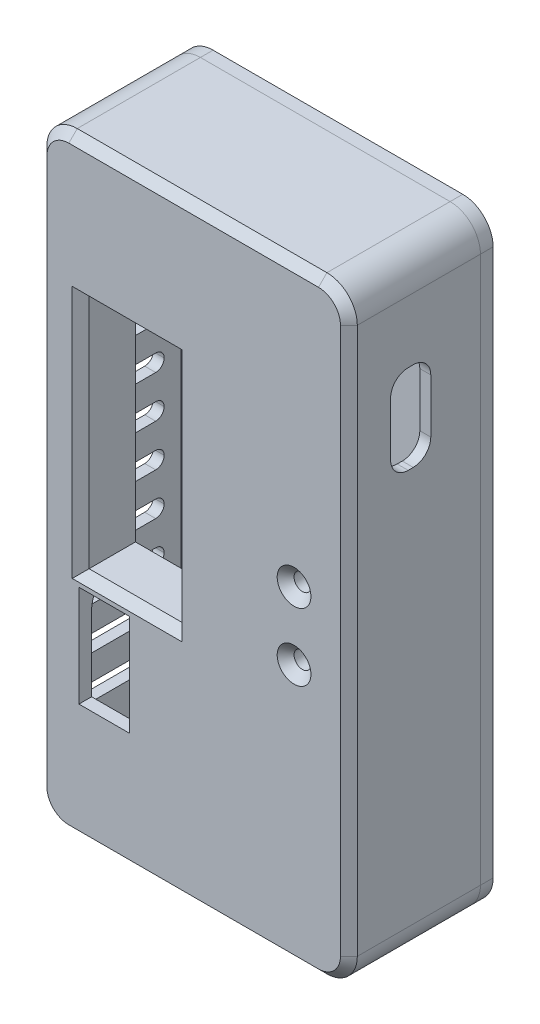
SolidWorks part; units mm, degrees
ref_plane "Front Plane" through (0, 0, 0) normal (0, 0, 1) x (1, 0, 0)
ref_plane "Top Plane" through (0, 0, 0) normal (0, 1, 0) x (1, 0, 0)
ref_plane "Right Plane" through (0, 0, 0) normal (1, 0, 0) x (0, 0, -1)
sketch "Sketch1" plane through (0, 0, 0) normal (0, 0, 1) x (1, 0, 0)
  line L0 (1226.9658, 17.5347) -> (1226.9658, 3.5347) construction
  line L1 (1226.9658, -40.4653) -> (1226.9658, -54.4653) construction
  line L2 (1260.1694, 17.5347) -> (1226.9658, 17.5347) construction
  line L3 (1263.7694, -50.8653) -> (1263.7694, 13.9347) construction
  line L4 (1226.9658, -54.4653) -> (1260.1694, -54.4653) construction
  line L5 (1226.9658, 17.5347) -> (1226.9658, 3.5347)
  line L6 (1226.9658, 3.5347) -> (1226.9658, -54.4653)
  line L7 (1260.1694, 17.5347) -> (1226.9658, 17.5347)
  line L8 (1263.7694, -50.8653) -> (1263.7694, 13.9347)
  line L9 (1226.9658, -54.4653) -> (1260.1694, -54.4653)
  line L10 (1228.2658, -53.1653) -> (1260.1694, -53.1653)
  line L11 (1262.4694, -50.8653) -> (1262.4694, 13.9347)
  line L12 (1260.1694, 16.2347) -> (1228.2658, 16.2347)
  line L13 (1228.2658, 16.2347) -> (1228.2658, 3.5347)
  line L14 (1228.2658, 3.5347) -> (1228.2658, -53.1653)
  arc A0 (1263.7694, 13.9347) -> (1260.1694, 17.5347) centre (1260.1694, 13.9347) ccw construction
  arc A1 (1260.1694, -54.4653) -> (1263.7694, -50.8653) centre (1260.1694, -50.8653) ccw construction
  arc A2 (1263.7694, 13.9347) -> (1260.1694, 17.5347) centre (1260.1694, 13.9347) ccw
  arc A3 (1260.1694, -54.4653) -> (1263.7694, -50.8653) centre (1260.1694, -50.8653) ccw
  arc A4 (1260.1694, -53.1653) -> (1262.4694, -50.8653) centre (1260.1694, -50.8653) ccw
  arc A5 (1262.4694, 13.9347) -> (1260.1694, 16.2347) centre (1260.1694, 13.9347) ccw
  dimension "D1" = 1.3
extrude "Boss-Extrude1" add sketch "Sketch1" along normal offset from surface (14.1005 mm away) 0.2 offset beyond the face yes
sketch "Sketch2" plane through (0, 0, 14.1005) normal (0, 0, 1) x (1, 0, 0)
  line L5 (1226.9658, 17.5347) -> (1226.9658, -54.4653)
  line L6 (1226.9658, -54.4653) -> (1260.1694, -54.4653)
  line L7 (1263.7694, -50.8653) -> (1263.7694, 13.9347)
  line L8 (1260.1694, 17.5347) -> (1226.9658, 17.5347)
  line L9 (1226.9658, 17.5347) -> (1226.9658, -54.4653)
  line L10 (1226.9658, -54.4653) -> (1260.1694, -54.4653)
  line L11 (1263.7694, -50.8653) -> (1263.7694, 13.9347)
  line L12 (1260.1694, 17.5347) -> (1226.9658, 17.5347)
  arc A2 (1260.1694, -54.4653) -> (1263.7694, -50.8653) centre (1260.1694, -50.8653) ccw
  arc A3 (1263.7694, 13.9347) -> (1260.1694, 17.5347) centre (1260.1694, 13.9347) ccw
  arc A4 (1260.1694, -54.4653) -> (1263.7694, -50.8653) centre (1260.1694, -50.8653) ccw
  arc A5 (1263.7694, 13.9347) -> (1260.1694, 17.5347) centre (1260.1694, 13.9347) ccw
  dimension "D1" = 0
extrude "Boss-Extrude2" add sketch "Sketch2" along normal blind 1.5
sketch "Sketch3" plane through (0, 0, 15.6005) normal (0, 0, 1) x (1, 0, 0)
  line L0 (1226.9658, -40.4653) -> (1226.9658, -54.4653) construction
  line L1 (1231.7658, -28.4653) -> (1237.7658, -28.4653)
  line L2 (1231.7658, -28.4653) -> (1231.7658, -40.4653)
  line L3 (1231.7658, -40.4653) -> (1237.7658, -40.4653)
  line L4 (1237.7658, -28.4653) -> (1237.7658, -40.4653)
  line L5 (1231.9658, -26.9653) -> (1242.9658, -26.9653)
  line L6 (1231.9658, -26.9653) -> (1231.9658, 1.0347)
  line L7 (1231.9658, 1.0347) -> (1242.9658, 1.0347)
  line L8 (1242.9658, -26.9653) -> (1242.9658, 1.0347)
  line L9 (1226.9658, -54.4653) -> (1260.1694, -54.4653) construction
  line L10 (1257.2694, -15.6653) -> (1257.2694, -23.6653) construction
  line L11 (1263.7694, -50.8653) -> (1263.7694, 13.9347) construction
  circle A0 centre (1257.2694, -23.6653) radius 1
  circle A1 centre (1257.2694, -15.6653) radius 1
  point P18 (1237.4658, -26.9653)
  dimension "D1" = 6
  dimension "D5" = 2
  dimension "D2" = 4.8
  dimension "D3" = 12
  dimension "D4" = 14
  dimension "D6" = 6.5
  dimension "D7" = 30.8
  dimension "D8" = 8
  dimension "D9" = 11
  dimension "D10" = 28
  dimension "D11" = 27.5
  dimension "D12" = 5
extrude "Cut-Extrude1" cut sketch "Sketch3" against normal blind 3.5
sketch "Sketch4" plane through (0, -54.4653, 0) normal (0, -1, 0) x (1, 0, 0)
  circle A2 centre (1247.2906, 10.2505) radius 3.8
  circle A3 centre (1247.2906, 10.2505) radius 3.8
  dimension "D1" = 0.7
extrude "Cut-Extrude2" cut sketch "Sketch4" against normal blind 3.5
sketch "Sketch5" plane through (1263.7694, 0, 0) normal (1, 0, 0) x (0, 0, -1)
  line L0 (-10.65, 4.4845) -> (-10.65, -1.8955)
  line L1 (-8.57, -3.9755) -> (-7.97, -3.9755)
  line L2 (-5.89, -1.8955) -> (-5.89, 0.7945)
  line L3 (-5.89, 0.7945) -> (-5.89, 4.4845)
  line L4 (-7.97, 6.5645) -> (-8.57, 6.5645)
  line L12 (-8.57, 5.5645) -> (-7.97, 5.5645)
  line L13 (-6.89, 4.4845) -> (-6.89, 0.7945)
  line L14 (-6.89, 0.7945) -> (-6.69, 0.7945)
  line L15 (-6.69, 0.7945) -> (-6.69, 4.4845)
  line L16 (-7.97, 5.7645) -> (-8.57, 5.7645)
  line L17 (-9.85, 4.4845) -> (-9.85, -1.8955)
  line L18 (-8.57, -3.1755) -> (-7.97, -3.1755)
  line L19 (-6.69, -1.8955) -> (-6.69, 0.7845)
  line L20 (-6.69, 0.7845) -> (-6.89, 0.7845)
  line L21 (-6.89, 0.7845) -> (-6.89, -1.8955)
  line L22 (-7.97, -2.9755) -> (-8.57, -2.9755)
  line L23 (-9.65, -1.8955) -> (-9.65, 4.4845)
  line L27 (-6.69, 0.7945) -> (-6.69, 4.4845) construction
  line L28 (-7.97, 5.7645) -> (-8.57, 5.7645) construction
  line L29 (-9.85, 4.4845) -> (-9.85, -1.8955) construction
  line L30 (-8.57, -3.1755) -> (-7.97, -3.1755) construction
  line L31 (-6.69, -1.8955) -> (-6.69, 0.7945) construction
  arc A0 (-8.57, 5.5645) -> (-9.65, 4.4845) centre (-8.57, 4.4845) ccw
  arc A1 (-6.89, 4.4845) -> (-7.97, 5.5645) centre (-7.97, 4.4845) ccw
  arc A2 (-6.69, 4.4845) -> (-7.97, 5.7645) centre (-7.97, 4.4845) ccw
  arc A3 (-8.57, 5.7645) -> (-9.85, 4.4845) centre (-8.57, 4.4845) ccw
  arc A4 (-9.85, -1.8955) -> (-8.57, -3.1755) centre (-8.57, -1.8955) ccw
  arc A5 (-7.97, -3.1755) -> (-6.69, -1.8955) centre (-7.97, -1.8955) ccw
  arc A6 (-7.97, -2.9755) -> (-6.89, -1.8955) centre (-7.97, -1.8955) ccw
  arc A7 (-9.65, -1.8955) -> (-8.57, -2.9755) centre (-8.57, -1.8955) ccw
  arc A10 (-6.69, 4.4845) -> (-7.97, 5.7645) centre (-7.97, 4.4845) ccw construction
  arc A11 (-8.57, 5.7645) -> (-9.85, 4.4845) centre (-8.57, 4.4845) ccw construction
  arc A12 (-9.85, -1.8955) -> (-8.57, -3.1755) centre (-8.57, -1.8955) ccw construction
  arc A13 (-7.97, -3.1755) -> (-6.69, -1.8955) centre (-7.97, -1.8955) ccw construction
  arc A16 (-10.65, -1.8955) -> (-8.57, -3.9755) centre (-8.57, -1.8955) ccw
  arc A17 (-7.97, -3.9755) -> (-5.89, -1.8955) centre (-7.97, -1.8955) ccw
  arc A18 (-5.89, 4.4845) -> (-7.97, 6.5645) centre (-7.97, 4.4845) ccw
  arc A19 (-8.57, 6.5645) -> (-10.65, 4.4845) centre (-8.57, 4.4845) ccw
  dimension "D1" = 0
  dimension "D2" = 0.8
extrude "Cut-Extrude3" cut sketch "Sketch5" against normal blind 3.5
fillet "Fillet1" radius 2.3 2 edges at (1228.2658, -53.1653, 7.0502) (1228.2658, 16.2347, 7.0502)
fillet "Fillet2" radius 3.6 2 edges at (1226.9658, -54.4653, 7.8002) (1226.9658, 17.5347, 7.8002)
sketch "Sketch6" plane through (0, 0, 14.1005) normal (0, 0, -1) x (-1, 0, 0)
  line L0 (-1243.9658, -27.9653) -> (-1230.9658, -27.9653)
  line L1 (-1230.9658, -27.9653) -> (-1230.9658, 2.0347)
  line L2 (-1230.9658, 2.0347) -> (-1243.9658, 2.0347)
  line L3 (-1243.9658, 2.0347) -> (-1243.9658, -27.9653)
  line L4 (-1231.9658, 1.0347) -> (-1242.9658, 1.0347)
  line L5 (-1231.9658, -26.9653) -> (-1231.9658, 1.0347)
  line L6 (-1242.9658, -26.9653) -> (-1231.9658, -26.9653)
  line L7 (-1242.9658, 1.0347) -> (-1242.9658, -26.9653)
  line L8 (-1231.9658, 1.0347) -> (-1242.9658, 1.0347)
  line L9 (-1231.9658, -26.9653) -> (-1231.9658, 1.0347)
  line L10 (-1242.9658, -26.9653) -> (-1231.9658, -26.9653)
  line L11 (-1242.9658, 1.0347) -> (-1242.9658, -26.9653)
  dimension "D1" = 0
  dimension "D2" = 1
extrude "Boss-Extrude3" add sketch "Sketch6" along normal blind 5
fillet "Fillet3" radius 3.6 4 edges at (1237.4658, -27.9653, 14.1005) (1230.9658, -12.9653, 14.1005) (1237.4658, 2.0347, 14.1005) (1243.9658, -12.9653, 14.1005)
chamfer "Chamfer1" distance 1 angle 45 4 edges at (1237.4658, 1.0347, 15.6005) (1242.9658, -12.9653, 15.6005) (1237.4658, -26.9653, 15.6005) (1231.9658, -12.9653, 15.6005)
sketch "Sketch7" plane through (0, 0, 14.1005) normal (0, 0, -1) x (-1, 0, 0)
  circle A0 centre (-1257.2694, -15.6653) radius 1 construction
  circle A1 centre (-1257.2694, -15.6653) radius 1
  circle A2 centre (-1257.2694, -23.6653) radius 1 construction
  circle A3 centre (-1257.2694, -23.6653) radius 1
  circle A4 centre (-1257.2694, -15.6653) radius 2
  circle A5 centre (-1257.2694, -23.6653) radius 2
  dimension "D1" = 1
  dimension "D2" = 1
extrude "Boss-Extrude4" add sketch "Sketch7" along normal blind 5
chamfer "Chamfer2" distance 1 angle 45 2 edges at (1258.2694, -15.6653, 15.6005) (1258.2694, -23.6653, 15.6005)
chamfer "Chamfer3" distance 1 angle 45 8 edges at (1226.9658, -18.4653, 15.6005) (1228.0202, -53.4108, 15.6005) (1228.0202, 16.4803, 15.6005) (1245.3676, -54.4653, 15.6005) (1245.3676, 17.5347, 15.6005) (1262.7149, -53.4108, 15.6005) (1262.7149, 16.4803, 15.6005) (1263.7694, -18.4653, 15.6005)
chamfer "Chamfer4" distance 1.5 angle 45 2 edges at (1259.2694, -23.6653, 14.1005) (1259.2694, -15.6653, 14.1005)
sketch "Sketch8" plane through (1226.9658, 0, 0) normal (-1, 0, 0) x (0, 0, 1)
  line L0 (0, -18.4653) -> (14.6005, -18.4653) construction
  line L1 (0, 13.9347) -> (0, -50.8653) construction
  line L2 (14.6005, -50.8653) -> (14.6005, 13.9347) construction
  line L3 (2, -14.4653) -> (12.6005, -14.4653)
  line L4 (2, -19.4653) -> (12.6005, -19.4653)
  line L5 (2, -19.4653) -> (2, -17.4653)
  line L6 (2, -17.4653) -> (12.6005, -17.4653)
  line L7 (12.6005, -19.4653) -> (12.6005, -17.4653)
  line L8 (2, -19.4653) -> (12.6005, -17.4653) construction
  line L9 (2, -17.4653) -> (12.6005, -19.4653) construction
  line L10 (12.6005, -14.4653) -> (12.6005, -12.4653)
  line L11 (2, -12.4653) -> (12.6005, -12.4653)
  line L12 (2, -14.4653) -> (2, -12.4653)
  line L13 (2, -9.4653) -> (12.6005, -9.4653)
  line L14 (12.6005, -9.4653) -> (12.6005, -7.4653)
  line L15 (2, -7.4653) -> (12.6005, -7.4653)
  line L16 (2, -9.4653) -> (2, -7.4653)
  line L17 (2, -4.4653) -> (12.6005, -4.4653)
  line L18 (12.6005, -4.4653) -> (12.6005, -2.4653)
  line L19 (2, -2.4653) -> (12.6005, -2.4653)
  line L20 (2, -4.4653) -> (2, -2.4653)
  line L21 (2, 0.5347) -> (12.6005, 0.5347)
  line L22 (12.6005, 0.5347) -> (12.6005, 2.5347)
  line L23 (2, 2.5347) -> (12.6005, 2.5347)
  line L24 (2, 0.5347) -> (2, 2.5347)
  line L25 (2, 5.5347) -> (12.6005, 5.5347)
  line L26 (12.6005, 5.5347) -> (12.6005, 7.5347)
  line L27 (2, 7.5347) -> (12.6005, 7.5347)
  line L28 (2, 5.5347) -> (2, 7.5347)
  line L29 (2, -24.4653) -> (12.6005, -24.4653)
  line L30 (12.6005, -24.4653) -> (12.6005, -22.4653)
  line L31 (2, -22.4653) -> (12.6005, -22.4653)
  line L32 (2, -24.4653) -> (2, -22.4653)
  line L33 (2, -29.4653) -> (12.6005, -29.4653)
  line L34 (12.6005, -29.4653) -> (12.6005, -27.4653)
  line L35 (2, -27.4653) -> (12.6005, -27.4653)
  line L36 (2, -29.4653) -> (2, -27.4653)
  line L37 (2, -34.4653) -> (12.6005, -34.4653)
  line L38 (12.6005, -34.4653) -> (12.6005, -32.4653)
  line L39 (2, -32.4653) -> (12.6005, -32.4653)
  line L40 (2, -34.4653) -> (2, -32.4653)
  line L41 (2, -39.4653) -> (12.6005, -39.4653)
  line L42 (12.6005, -39.4653) -> (12.6005, -37.4653)
  line L43 (2, -37.4653) -> (12.6005, -37.4653)
  line L44 (2, -39.4653) -> (2, -37.4653)
  line L45 (2, -44.4653) -> (12.6005, -44.4653)
  line L46 (12.6005, -44.4653) -> (12.6005, -42.4653)
  line L47 (2, -42.4653) -> (12.6005, -42.4653)
  line L48 (2, -44.4653) -> (2, -42.4653)
  point P6 (7.3002, -18.4653)
  dimension "D1" = 2
  dimension "D2" = 2
  dimension "D4" = 3
  dimension "D5" = 6
  dimension "D6" = 3
  dimension "D3" = 6
extrude "Cut-Extrude4" cut sketch "Sketch8" against normal blind 2
fillet "Fillet4" radius 1 44 edges at (1227.6158, 0.5347, 2) (1227.6158, -4.4653, 2) (1227.6158, -9.4653, 2) (1227.6158, -14.4653, 2) (1227.6158, -19.4653, 2) (1227.6158, -24.4653, 2) (1227.6158, -29.4653, 2) (1227.6158, -34.4653, 2) (1227.6158, -39.4653, 2) (1227.6158, -44.4653, 2) (1227.6158, -42.4653, 2) (1227.6158, -37.4653, 2) (1227.6158, -32.4653, 2) (1227.6158, -27.4653, 2) (1227.6158, -22.4653, 2) (1227.6158, -17.4653, 2) (1227.6158, -12.4653, 2) (1227.6158, -7.4653, 2) (1227.6158, -2.4653, 2) (1227.6158, 2.5347, 2) (1227.6158, 2.5347, 12.6005) (1227.6158, -2.4653, 12.6005) (1227.6158, -7.4653, 12.6005) (1227.6158, -12.4653, 12.6005) (1227.6158, -17.4653, 12.6005) (1227.6158, -22.4653, 12.6005) (1227.6158, -27.4653, 12.6005) (1227.6158, -32.4653, 12.6005) (1227.6158, -37.4653, 12.6005) (1227.6158, -42.4653, 12.6005) (1227.6158, -44.4653, 12.6005) (1227.6158, -39.4653, 12.6005) (1227.6158, -34.4653, 12.6005) (1227.6158, -29.4653, 12.6005) (1227.6158, -24.4653, 12.6005) (1227.6158, -19.4653, 12.6005) (1227.6158, -14.4653, 12.6005) (1227.6158, -9.4653, 12.6005) (1227.6158, -4.4653, 12.6005) (1227.6158, 0.5347, 12.6005) (1227.6158, 5.5347, 12.6005) (1227.6158, 7.5347, 12.6005) (1227.6158, 5.5347, 2) (1227.6158, 7.5347, 2)
sketch "Sketch9" plane through (0, 0, 0) normal (0, 0, -1) x (-1, 0, 0)
  line L5 (-1260.1694, -54.4653) -> (-1230.5658, -54.4653)
  line L6 (-1226.9658, -50.8653) -> (-1226.9658, 13.9347)
  line L7 (-1230.5658, 17.5347) -> (-1260.1694, 17.5347)
  line L8 (-1263.7694, 13.9347) -> (-1263.7694, -50.8653)
  line L9 (-1260.1694, -54.4653) -> (-1230.5658, -54.4653)
  line L10 (-1226.9658, -50.8653) -> (-1226.9658, 13.9347)
  line L11 (-1230.5658, 17.5347) -> (-1260.1694, 17.5347)
  line L12 (-1263.7694, 13.9347) -> (-1263.7694, -50.8653)
  arc A4 (-1230.5658, -54.4653) -> (-1226.9658, -50.8653) centre (-1230.5658, -50.8653) ccw
  arc A5 (-1226.9658, 13.9347) -> (-1230.5658, 17.5347) centre (-1230.5658, 13.9347) ccw
  arc A6 (-1260.1694, 17.5347) -> (-1263.7694, 13.9347) centre (-1260.1694, 13.9347) ccw
  arc A7 (-1263.7694, -50.8653) -> (-1260.1694, -54.4653) centre (-1260.1694, -50.8653) ccw
  arc A8 (-1230.5658, -54.4653) -> (-1226.9658, -50.8653) centre (-1230.5658, -50.8653) ccw
  arc A9 (-1226.9658, 13.9347) -> (-1230.5658, 17.5347) centre (-1230.5658, 13.9347) ccw
  arc A10 (-1260.1694, 17.5347) -> (-1263.7694, 13.9347) centre (-1260.1694, 13.9347) ccw
  arc A11 (-1263.7694, -50.8653) -> (-1260.1694, -54.4653) centre (-1260.1694, -50.8653) ccw
  dimension "D1" = 0
extrude "Boss-Extrude5" add sketch "Sketch9" along normal blind 1.5 separate body
sketch "Sketch10" plane through (0, 0, 0) normal (0, 0, 1) x (1, 0, 0)
  line L0 (1245.3676, 17.5347) -> (1245.3676, 16.1347) construction
  line L1 (1235.3676, 16.1347) -> (1255.3676, 16.1347)
  line L2 (1235.3676, 16.1347) -> (1235.3676, 13.1347)
  line L3 (1235.3676, 13.1347) -> (1255.3676, 13.1347)
  line L4 (1255.3676, 16.1347) -> (1255.3676, 13.1347)
  line L5 (1235.3676, -50.0653) -> (1255.3676, -50.0653)
  line L6 (1235.3676, -50.0653) -> (1235.3676, -53.0653)
  line L7 (1235.3676, -53.0653) -> (1255.3676, -53.0653)
  line L8 (1255.3676, -50.0653) -> (1255.3676, -53.0653)
  line L9 (1230.5658, 17.5347) -> (1260.1694, 17.5347) construction
  line L10 (1245.3676, 16.1347) -> (1245.3676, -50.0653) construction
  line L12 (1260.1694, 16.2347) -> (1230.5658, 16.2347) construction
  line L13 (1230.5658, -53.1653) -> (1260.1694, -53.1653) construction
  dimension "D1" = 3
  dimension "D2" = 3
  dimension "D3" = 20
  dimension "D4" = 0.1
  dimension "D5" = 0.1
extrude "Boss-Extrude6" add sketch "Sketch10" along normal blind 2
sketch "Sketch11" plane through (0, 0, -1.5) normal (0, 0, -1) x (-1, 0, 0)
  circle A0 centre (-1257.7694, -47.4653) radius 1.25 construction
  circle A1 centre (-1257.7694, -47.4653) radius 1.25
  circle A2 centre (-1234.7694, -47.4653) radius 1.25 construction
  circle A3 centre (-1234.7694, -47.4653) radius 1.25
  circle A4 centre (-1257.7694, 10.5347) radius 1.25 construction
  circle A5 centre (-1257.7694, 10.5347) radius 1.25
  circle A6 centre (-1234.7694, 10.5347) radius 1.25 construction
  circle A7 centre (-1234.7694, 10.5347) radius 1.25
extrude "Cut-Extrude5" cut sketch "Sketch11" against normal blind 2
